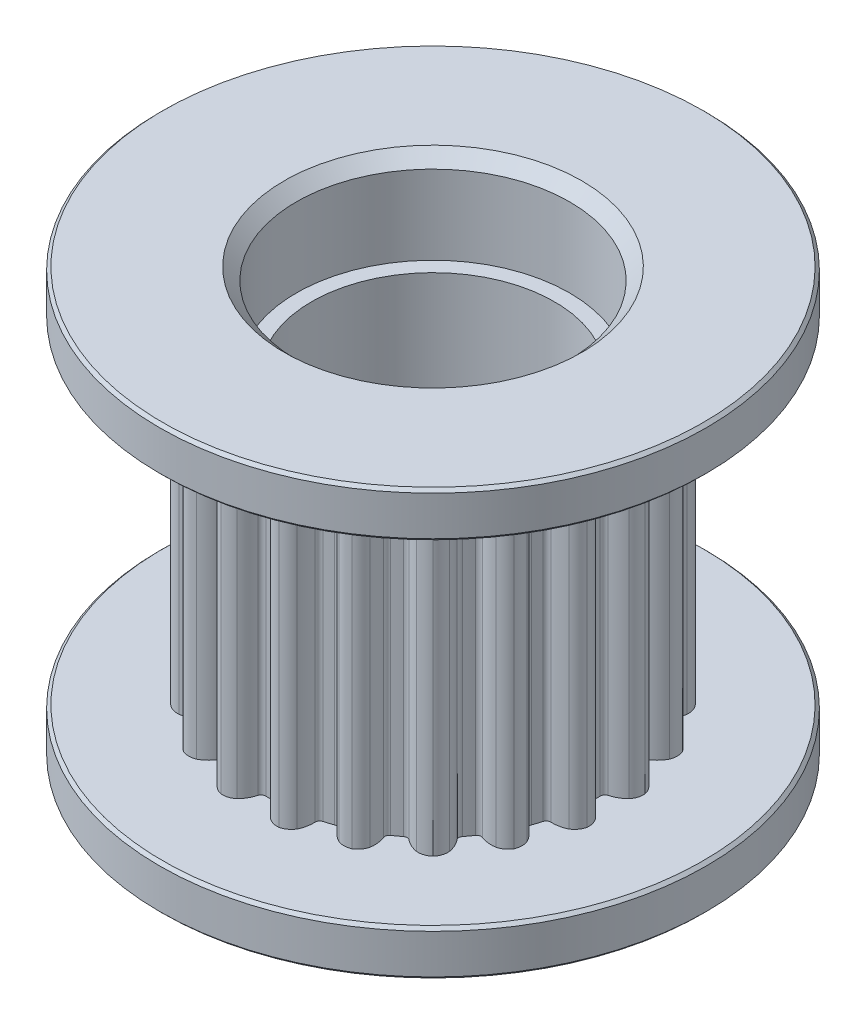
SolidWorks part; units mm, degrees
material "6061 Alloy"
ref_plane "Front Plane" through (0, 0, 0) normal (0, 0, 1) x (1, 0, 0)
ref_plane "Top Plane" through (0, 0, 0) normal (0, 1, 0) x (1, 0, 0)
ref_plane "Right Plane" through (0, 0, 0) normal (1, 0, 0) x (0, 0, -1)
sketch "Body Sketch" plane through (0, 0, 0) normal (0, 0, 1) x (1, 0, 0)
  line L0 (6.11, -5.5) -> (6.11, 5.5)
  line L1 (6.11, 5.5) -> (9, 5.5)
  line L2 (9, 5.5) -> (9, 7)
  line L3 (9, 7) -> (4.5, 7)
  line L4 (4.5, 7) -> (4.5, 4)
  line L5 (4.5, 4) -> (4, 4)
  line L6 (4, 4) -> (4, -4)
  line L7 (4, -4) -> (4.5, -4)
  line L8 (4.5, -4) -> (4.5, -7)
  line L9 (4.5, -7) -> (9, -7)
  line L10 (9, -7) -> (9, -5.5)
  line L11 (9, -5.5) -> (6.11, -5.5)
  line L12 (0, 0) -> (4, 0) construction
  line L13 (0, 7) -> (0, -7) construction
  dimension "BearingOD" = 9
  dimension "Height" = 14
  dimension "FlangeHeight" = 1.5
  dimension "BearingHeight" = 3
  dimension "BearingRestDiaControl" = 0.5
  dimension "RefBodyInnerDiameter" = 8
  dimension "FlangeDiaControl" = 4.5
  dimension "RefFlangeDia" = 18
  dimension "BeltPathDiaControl" = 1.61
  dimension "RefBeltPathDia" = 12.22
revolve "Body" add sketch "Body Sketch" angle 360 about L13
sketch "GT2 Profile Sketch" plane through (0, 0, 0) normal (0, 1, 0) x (1, 0, 0)
  line L1 (0, -6.11) -> (0, -5.36) construction
  line L2 (-0.9955, -6.0283) -> (-0.8733, -5.2884) construction
  line L3 (0, 0) -> (-0.8733, -5.2884) construction
  line L4 (0.9955, -6.0283) -> (0, 0) construction
  arc A3 (0.2997, -5.4688) -> (0.1507, -5.3579) centre (0.1549, -5.5078) ccw
  arc A4 (-0.9955, -6.0283) -> (0.9955, -6.0283) centre (0, 0) ccw
  arc A5 (-0.2997, -5.4688) -> (-0.1507, -5.3579) centre (-0.1549, -5.5078) cw
  arc A6 (-0.2997, -5.4688) -> (-0.5497, -5.907) centre (-1.2653, -5.2085) cw
  circle A7 centre (0, 0) radius 6.11 construction
  arc A8 (-0.1507, -5.3579) -> (0.1507, -5.3579) centre (0, 0) ccw
  arc A9 (-0.5497, -5.907) -> (-0.9955, -6.0283) centre (-0.9051, -5.4808) cw
  arc A10 (0.2997, -5.4688) -> (0.5497, -5.907) centre (1.2653, -5.2085) ccw
  arc A11 (0.5497, -5.907) -> (0.9955, -6.0283) centre (0.9051, -5.4808) ccw
  circle A12 centre (0, 0) radius 5.36 construction
  dimension "BottomRadius" = 0.15
  dimension "MidRadius" = 1
  dimension "TopRadius" = 0.555
  dimension "Height" = 0.75
  dimension "XDistMidRadius" = 0.4
  dimension "ArcLengthAngle" = 18.755
  dimension "ArcLength" = 2
sketch "Thru Bore Sketch" [suppressed] plane through (0, 0, 0) normal (0, 1, 0) x (1, 0, 0)
  circle A0 centre (0, 0) radius 4
  circle A2 centre (0, 0) radius 4 construction
extrude "Thru Bore" [suppressed] cut sketch "Thru Bore Sketch" against normal through all both and the other way through all
extrude "GT2 Profile" cut sketch "GT2 Profile Sketch" against normal up to surface and the other way up to surface up to face at (0, -5.5, 6.11) other way up to face at (0, 5.5, 9)
pattern_circular "GT2 Groove Circular Pattern" count 20 over 360 about axis through (0, 7, 0) along (0, 1, 0) of "GT2 Profile"
chamfer "Inner Chamfer" distance 0.4 angle 45 2 edges at (0, -7, 4.5) (0, 7, 4.5)
chamfer "Outer Chamfer" distance 0.1 angle 45 4 edges at (0, -7, 9) (0, -5.5, 9) (0, 5.5, 9) (0, 7, 9)
equation "\"NumTeeth@GT2 Groove Circular Pattern\"=int(360/\"ArcLengthAngle@GT2 Profile Sketch\")+1"
